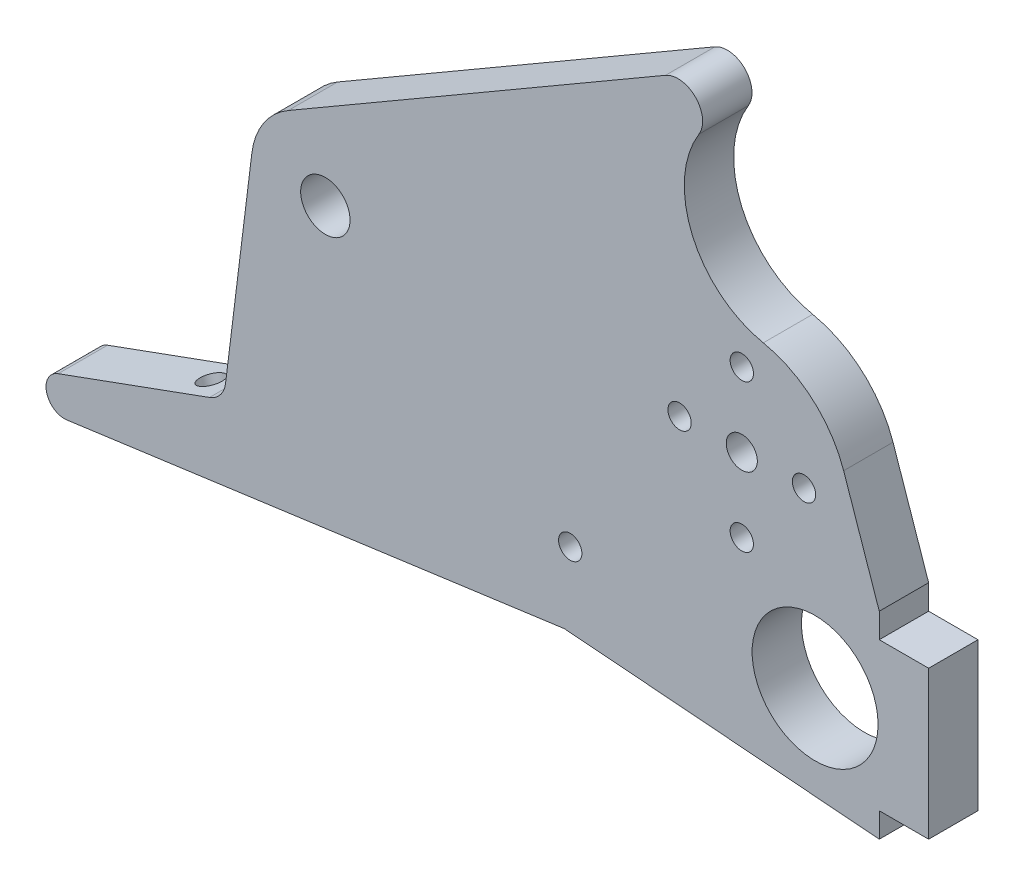
SolidWorks part; units mm, degrees
ref_plane "Front Plane" through (0, 0, 0) normal (0, 0, 1) x (1, 0, 0)
ref_plane "Top Plane" through (0, 0, 0) normal (0, 1, 0) x (1, 0, 0)
ref_plane "Right Plane" through (0, 0, 0) normal (1, 0, 0) x (0, 0, -1)
sketch "Sketch1" plane through (0, 0, 0) normal (0, 0, 1) x (1, 0, 0)
  line L0 (12.2605, 58.6546) -> (-36.2799, 30.4615)
  line L1 (0, -55) -> (0, 55) construction
  line L2 (39.751, 9.525) -> (46.101, 9.525)
  line L3 (39.751, 9.525) -> (39.751, -9.525) construction
  line L4 (39.751, -9.525) -> (46.101, -9.525)
  line L5 (46.101, 9.525) -> (46.101, -9.525)
  line L6 (14.0686, 21.567) -> (30.0686, 21.567) construction
  line L7 (22.0686, 31.067) -> (22.0686, 12.067) construction
  line L8 (39.751, 9.525) -> (39.751, 12.7)
  line L9 (39.751, -9.525) -> (39.751, -12.7)
  line L10 (-36.9877, 14.4425) -> (-5.4917, -7.7825)
  line L11 (39.751, -12.7) -> (-0.7513, -9.4953)
  line L12 (-18.0656, 110.4417) -> (26016.8979, -39640.6484) construction
  line L14 (22.0686, 21.567) -> (34.7171, 29.8512) construction
  line L15 (39.751, 12.7) -> (35.1696, 26.0597)
  line L16 (22.0686, 21.567) -> (23.8659, 17.4552)
  line L17 (23.8659, 17.4552) -> (27.6159, 8.8765) construction
  line L18 (27.6159, 8.8765) -> (28.2517, 7.4219)
  line L19 (28.2517, 7.4219) -> (31.496, 0) construction
  circle A2 centre (31.496, 0) radius 19.05 construction
  circle A3 centre (-31.496, 0) radius 19.05 construction
  circle A4 centre (-31.496, 22.225) radius 38.1 construction
  circle A5 centre (0, 0) radius 1.5
  circle A6 centre (22.0686, 31.067) radius 1.5
  circle A7 centre (30.0686, 21.567) radius 1.5
  circle A8 centre (22.0686, 12.067) radius 1.5
  circle A9 centre (14.0686, 21.567) radius 1.5
  circle A11 centre (-31.496, 22.225) radius 3.175
  arc A12 (-36.2799, 30.4615) -> (-36.9877, 14.4425) centre (-31.496, 22.225) ccw
  arc A19 (35.1696, 26.0597) -> (24.8346, 35.138) centre (22.0686, 21.567) ccw
  arc A20 (16.5583, 54.2437) -> (12.2605, 58.6546) centre (13.8552, 55.9091) ccw
  arc A21 (-5.4917, -7.7825) -> (-0.7513, -9.4953) centre (0, 0) ccw
  arc A22 (16.5583, 54.2437) -> (24.8346, 35.138) centre (27.371, 47.5822) ccw
  arc A23 (-36.9877, 14.4425) -> (-36.2799, 30.4615) centre (-31.496, 22.225) ccw construction
  circle A31 centre (22.0686, 21.567) radius 2
  arc A33 (4.086, 8.6041) -> (-5.4917, -7.7825) centre (0, 0) ccw construction
  arc A34 (-0.7513, -9.4953) -> (4.086, 8.6041) centre (0, 0) ccw construction
  arc A35 (24.8346, 35.138) -> (15.0556, 9.6238) centre (22.0686, 21.567) ccw construction
  arc A36 (15.0556, 9.6238) -> (35.1696, 26.0597) centre (22.0686, 21.567) ccw construction
  circle A37 centre (31.496, 0) radius 8.1
  point P2 (33.6547, 29.1554)
  point P10 (46.101, 0)
  point P13 (-31.496, -19.05)
  point P24 (-31.496, -15.875)
  point P26 (22.0686, 21.567)
  point P29 (22.0686, 21.567)
  point P37 (42.926, -9.525)
  dimension "D7" = 38.1
  dimension "D8" = 76.2
  dimension "D11" = 3
  dimension "D13" = 3
  dimension "D14" = 27.7
  dimension "D16" = 6.35
  dimension "D17" = 19.05
  dimension "D21" = 6.35
  dimension "D22" = 1.5875
  dimension "D23" = 16.2
  dimension "D25" = 56.134
  dimension "D26" = 4
  dimension "D19" = 19.05
  dimension "D24" = 12.7
  dimension "D3" = 19.05
  dimension "D4" = 6.35
  dimension "D5" = 11.43
  dimension "D6" = 62.992
  dimension "D9" = 3.175
  dimension "D10" = 19
  dimension "D12" = 16
  dimension "D15" = 1.27
  dimension "D18" = 53.5686
  dimension "D20" = 3.175
extrude "Boss-Extrude1" add sketch "Sketch1" along normal mid plane 6.35 contours L10 L11 L9 L4 L5 L2 L8 A12 A20 A6 A7 A8 A9 A11 region at (3.5012, 18.9329, 0)
sketch "Sketch2" plane through (0, 0, 3.175) normal (0, 0, 1) x (1, 0, 0)
  line L0 (-46.398, -6.562) -> (-65.8615, -13.6461) construction
  line L1 (-46.398, -6.562) -> (-65.8615, -13.6461)
  line L2 (-44.3329, -3.9682) -> (-40.949, 23.3941)
  line L3 (-64.7244, -18.2431) -> (-0.7513, -9.4953)
  line L4 (-36.9877, 14.4425) -> (-5.4917, -7.7825) construction
  line L5 (-36.9877, 14.4425) -> (-5.4917, -7.7825)
  arc A0 (-65.8615, -13.6461) -> (-64.8428, -18.2563) centre (-65.0471, -15.8838) ccw construction
  arc A1 (-65.8615, -13.6461) -> (-64.7244, -18.2431) centre (-65.0471, -15.8838) ccw
  arc A2 (-5.4917, -7.7825) -> (-0.7513, -9.4953) centre (0, 0) ccw construction
  arc A3 (-46.398, -6.562) -> (-44.3329, -3.9682) centre (-47.4839, -3.5785) ccw
  arc A4 (-36.2799, 30.4615) -> (-36.9877, 14.4425) centre (-31.496, 22.225) ccw construction
  arc A5 (-5.4917, -7.7825) -> (-0.7513, -9.4953) centre (0, 0) ccw
  arc A6 (-40.949, 23.3941) -> (-36.9877, 14.4425) centre (-31.496, 22.225) ccw
  dimension "D1" = 3.175
extrude "Boss-Extrude2" add sketch "Sketch2" against normal up to surface (6.35 mm away) up to face at (39.596, 0, -3.175)
sketch "Sketch3" plane through (-3.3185, 9.1176, 0) normal (-0.342, 0.9397, 0) x (0.9397, 0.342, 0)
  line L0 (-45.8442, 3.175) -> (-45.8442, -3.175) construction
  line L1 (-49.0192, 0) -> (-45.8442, 0) construction
  circle A0 centre (-49.0192, 0) radius 1.5
  dimension "D1" = 3
  dimension "D2" = 3.175
extrude "Cut-Extrude1" cut sketch "Sketch3" against normal blind 6
